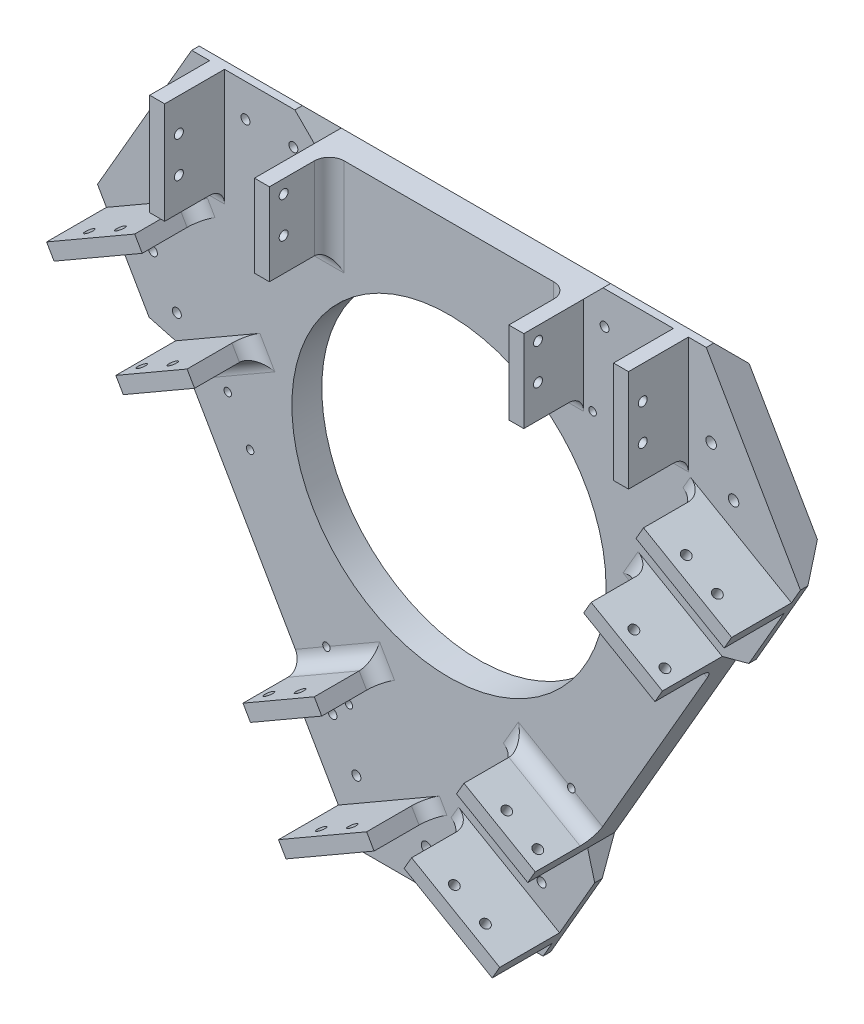
SolidWorks part; units mm, degrees
ref_plane "Plan de face" through (0, 0, 0) normal (0, 0, 1) x (1, 0, 0)
ref_plane "Plan de dessus" through (0, 0, 0) normal (0, 1, 0) x (1, 0, 0)
ref_plane "Plan de droite" through (0, 0, 0) normal (1, 0, 0) x (0, 0, -1)
sketch "Esquisse1" plane through (0, 0, 0) normal (0, 0, 1) x (1, 0, 0)
  line L0 (-85.9808, 85.9808) -> (85.9808, 85.9808)
  line L1 (85.9808, 85.9808) -> (117.4519, 31.4711)
  line L2 (117.4519, 31.4711) -> (31.4711, -117.4519)
  line L3 (31.4711, -117.4519) -> (-31.4711, -117.4519)
  line L4 (-31.4711, -117.4519) -> (-117.4519, 31.4711)
  line L5 (-117.4519, 31.4711) -> (-85.9808, 85.9808)
  line L6 (0, 85.9808) -> (0, -85.9808) construction
  circle A0 centre (0, 0) radius 52.5
  circle A1 centre (0, 0) radius 85.9808 construction
  point P6 (0, -117.4519)
  point P11 (0, 85.9808)
  point P12 (-74.4615, -42.9904)
  point P13 (74.4615, -42.9904)
  dimension "D1" = 105
  dimension "D2" = 117.4519
extrude "Boss.-Extru.1" add sketch "Esquisse1" along normal blind 10
sketch "Esquisse2" plane through (0, 0, 10) normal (0, 0, 1) x (1, 0, 0)
  line L0 (85.9808, 85.9808) -> (-85.9808, 85.9808) construction
  line L1 (80, 85.9808) -> (75, 85.9808)
  line L2 (80, 85.9808) -> (80, 51.9808)
  line L3 (80, 51.9808) -> (75, 51.9808)
  line L4 (75, 85.9808) -> (75, 51.9808)
  line L5 (80, 85.9808) -> (85.9808, 85.9808) construction
  line L6 (45, 85.9808) -> (40, 85.9808)
  line L7 (45, 85.9808) -> (45, 51.9808)
  line L8 (45, 51.9808) -> (40, 51.9808)
  line L9 (40, 85.9808) -> (40, 51.9808)
  line L10 (-40, 85.9808) -> (-45, 85.9808)
  line L11 (-40, 85.9808) -> (-40, 51.9808)
  line L12 (-40, 51.9808) -> (-45, 51.9808)
  line L13 (-45, 85.9808) -> (-45, 51.9808)
  line L14 (-75, 85.9808) -> (-80, 85.9808)
  line L15 (-75, 85.9808) -> (-75, 51.9808)
  line L16 (-75, 51.9808) -> (-80, 51.9808)
  line L17 (-80, 85.9808) -> (-80, 51.9808)
  line L18 (-85.9808, 85.9808) -> (-80, 85.9808) construction
  line L19 (34.4615, -112.2724) -> (5.0167, -95.2724)
  line L20 (34.4615, -112.2724) -> (36.9615, -107.9423)
  line L21 (36.9615, -107.9423) -> (7.5167, -90.9423)
  line L22 (5.0167, -95.2724) -> (7.5167, -90.9423)
  line L23 (51.9615, -81.9615) -> (22.5167, -64.9615)
  line L24 (51.9615, -81.9615) -> (54.4615, -77.6314)
  line L25 (54.4615, -77.6314) -> (25.0167, -60.6314)
  line L26 (22.5167, -64.9615) -> (25.0167, -60.6314)
  line L27 (94.4615, -8.3494) -> (65.0167, 8.6506)
  line L28 (94.4615, -8.3494) -> (96.9615, -4.0192)
  line L29 (96.9615, -4.0192) -> (67.5167, 12.9808)
  line L30 (65.0167, 8.6506) -> (67.5167, 12.9808)
  line L31 (111.9615, 21.9615) -> (82.5167, 38.9615)
  line L32 (111.9615, 21.9615) -> (114.4615, 26.2917)
  line L33 (114.4615, 26.2917) -> (85.0167, 43.2917)
  line L34 (82.5167, 38.9615) -> (85.0167, 43.2917)
  line L35 (-114.4615, 26.2917) -> (-85.0167, 43.2917)
  line L36 (-114.4615, 26.2917) -> (-111.9615, 21.9615)
  line L37 (-111.9615, 21.9615) -> (-82.5167, 38.9615)
  line L38 (-85.0167, 43.2917) -> (-82.5167, 38.9615)
  line L39 (-96.9615, -4.0192) -> (-67.5167, 12.9808)
  line L40 (-96.9615, -4.0192) -> (-94.4615, -8.3494)
  line L41 (-94.4615, -8.3494) -> (-65.0167, 8.6506)
  line L42 (-67.5167, 12.9808) -> (-65.0167, 8.6506)
  line L43 (-54.4615, -77.6314) -> (-25.0167, -60.6314)
  line L44 (-54.4615, -77.6314) -> (-51.9615, -81.9615)
  line L45 (-51.9615, -81.9615) -> (-22.5167, -64.9615)
  line L46 (-25.0167, -60.6314) -> (-22.5167, -64.9615)
  line L47 (-36.9615, -107.9423) -> (-7.5167, -90.9423)
  line L48 (-36.9615, -107.9423) -> (-34.4615, -112.2724)
  line L49 (-34.4615, -112.2724) -> (-5.0167, -95.2724)
  line L50 (-7.5167, -90.9423) -> (-5.0167, -95.2724)
  point P56 (0, 0)
  dimension "D1" = 5
  dimension "D2" = 30
  dimension "D3" = 30
  dimension "D4" = 34
  dimension "D5" = 80
  dimension "D6" = 3
extrude "Boss.-Extru.2" add sketch "Esquisse2" along normal blind 20
fillet "Congé1" radius 5 18 edges at (-40, 68.9808, 10) (-42.5, 51.9808, 10) (-77.5, 51.9808, 10) (-83.7667, 41.1266, 10) (-79.7391, 0.1506, 10) (-66.2667, 10.8157, 10) (-39.7391, -69.1314, 10) (-23.7667, -62.7965, 10) (-6.2667, -93.1073, 10) (6.2667, -93.1073, 10) (23.7667, -62.7965, 10) (39.7391, -69.1314, 10) (79.7391, 0.1506, 10) (66.2667, 10.8157, 10) (83.7667, 41.1266, 10) (77.5, 51.9808, 10) (42.5, 51.9808, 10) (40, 68.9808, 10)
sketch "Esquisse3" plane through (-80, 0, 0) normal (-1, 0, 0) x (0, 0, 1)
  line L0 (30, 51.9808) -> (15, 51.9808) construction
  line L1 (10, 85.9808) -> (10, 46.9808) construction
  circle A0 centre (25.25, 74.9808) radius 1.5
  circle A1 centre (25.25, 62.9808) radius 1.5
  dimension "D1" = 3
  dimension "D2" = 12
  dimension "D3" = 11
  dimension "D4" = 15.25
extrude "Enlèv. mat.-Extru.1" cut sketch "Esquisse3" against normal through all
sketch "Esquisse4" plane through (0, 0, 0) normal (0, 0, -1) x (-1, 0, 0)
  line L0 (45, 85.9808) -> (75, 85.9808) construction
  line L1 (45, 85.9808) -> (75, 85.9808) construction
  line L2 (68, 74.9808) -> (52, 74.9808) construction
  line L3 (60, 74.9808) -> (60, 85.9808) construction
  line L4 (-75, 85.9808) -> (-45, 85.9808) construction
  line L5 (-75, 85.9808) -> (-45, 85.9808) construction
  line L6 (-52, 74.9808) -> (-68, 74.9808) construction
  line L7 (-60, 74.9808) -> (-60, 85.9808) construction
  circle A0 centre (68, 74.9808) radius 1.5
  circle A1 centre (52, 74.9808) radius 1.5
  circle A2 centre (-52, 74.9808) radius 1.5
  circle A3 centre (-68, 74.9808) radius 1.5
  dimension "D1" = 3
  dimension "D2" = 16
  dimension "D3" = 11
extrude "Enlèv. mat.-Extru.2" cut sketch "Esquisse4" against normal up to next
sketch "Esquisse5" plane through (0, 0, 0) normal (0, 0, -1) x (-1, 0, 0)
  circle A0 centre (68, 74.9808) radius 3
  circle A1 centre (52, 74.9808) radius 3
  circle A2 centre (-52, 74.9808) radius 3
  circle A3 centre (-68, 74.9808) radius 3
  dimension "D1" = 6
extrude "Enlèv. mat.-Extru.3" cut sketch "Esquisse5" against normal blind 4.25
sketch "Esquisse6" plane through (0, 0, 0) normal (0, 0, -1) x (-1, 0, 0)
  line L0 (-85.9808, 85.9808) -> (85.9808, 85.9808) construction
  line L1 (45, 85.9808) -> (-45, 85.9808)
  line L2 (45, 85.9808) -> (45, 79.4808)
  line L3 (45, 79.4808) -> (-45, 79.4808)
  line L4 (-45, 85.9808) -> (-45, 79.4808)
  dimension "D1" = 6.5
extrude "Enlèv. mat.-Extru.4" cut sketch "Esquisse6" against normal up to next
pattern_circular "Répétition circulaire3" count 3 over 360 about axis through (0, 0, 0) along (0, 0, 1) of "Enlèv. mat.-Extru.1", "Enlèv. mat.-Extru.3", "Enlèv. mat.-Extru.2", "Enlèv. mat.-Extru.4"
chamfer "Chanfrein1" distance 6.5 angle 45 18 edges at (-49.1469, -80.3365, 10) (45, 82.7308, 10) (-45, 85.9808, 5) (45, 85.9808, 5) (-45, 82.7308, 0) (45, 82.7308, 0) (-45, 82.7308, 10) (-51.9615, -81.9615, 5) (-94.1469, -2.3942, 10) (-96.9615, -4.0192, 5) (-49.1469, -80.3365, 0) (-94.1469, -2.3942, 0) (96.9615, -4.0192, 5) (49.1469, -80.3365, 10) (51.9615, -81.9615, 5) (94.1469, -2.3942, 0) (49.1469, -80.3365, 0) (94.1469, -2.3942, 10)
chamfer "Chanfrein2" distance 7.5 angle 45 3 edges at (-68.7404, 85.9808, 0) (108.8317, 16.5405, 0) (-108.8317, 16.5405, 0)
sketch "Esquisse7" plane through (0, 0, 0) normal (0, 0, -1) x (-1, 0, 0)
  line L0 (95.1157, 46.2548) -> (87.6157, 59.2452) construction
  line L1 (91.3657, 52.75) -> (101.7163, 58.726) construction
  line L2 (90.3109, 78.4808) -> (113.1218, 38.9711) construction
  circle A0 centre (95.1157, 46.2548) radius 1.75
  circle A1 centre (87.6157, 59.2452) radius 1.75
  dimension "D1" = 3.5
  dimension "D2" = 11.9519
  dimension "D3" = 15
extrude "Enlèv. mat.-Extru.5" cut sketch "Esquisse7" against normal up to next
sketch "Esquisse8" plane through (0, 0, 0) normal (0, 0, -1) x (-1, 0, 0)
  circle A0 centre (95.1157, 46.2548) radius 3.5
  circle A1 centre (87.6157, 59.2452) radius 3.5
  dimension "D1" = 7
extrude "Enlèv. mat.-Extru.6" cut sketch "Esquisse8" against normal blind 4
pattern_circular "Répétition circulaire4" count 3 over 360 about axis through (0, 0, 0) along (0, 0, 1) of "Enlèv. mat.-Extru.6", "Enlèv. mat.-Extru.5"
sketch "Esquisse9" plane through (0, 0, 0) normal (0, 0, -1) x (-1, 0, 0)
  line L0 (0, 0) -> (67.9663, -39.2404) construction
  line L1 (22.8109, -117.4519) -> (113.1218, 38.9711) construction
  line L2 (0, 0) -> (-67.9663, -39.2404) construction
  line L3 (-113.1218, 38.9711) -> (-22.8109, -117.4519) construction
  line L4 (33.4401, -77.0417) -> (40.9401, -64.0513) construction
  line L5 (40.9401, -64.0513) -> (66.4401, -19.884) construction
  line L6 (66.4401, -19.884) -> (73.9401, -6.8936) construction
  line L7 (-73.9401, -6.8936) -> (-66.4401, -19.884) construction
  line L8 (-66.4401, -19.884) -> (-40.9401, -64.0513) construction
  line L9 (-40.9401, -64.0513) -> (-33.4401, -77.0417) construction
  line L10 (-48, 48.4808) -> (-58, 48.4808) construction
  line L11 (-58, 48.4808) -> (-58, 38.4808) construction
  line L12 (48, 48.4808) -> (58, 48.4808) construction
  line L13 (58, 48.4808) -> (58, 38.4808) construction
  line L14 (-48, 48.4808) -> (48, 48.4808) construction
  line L15 (90.3109, 78.4808) -> (-90.3109, 78.4808) construction
  circle A0 centre (33.4401, -77.0417) radius 1.25
  circle A1 centre (40.9401, -64.0513) radius 1.25
  circle A2 centre (66.4401, -19.884) radius 1.25
  circle A3 centre (73.9401, -6.8936) radius 1.25
  circle A4 centre (-73.9401, -6.8936) radius 1.25
  circle A5 centre (-66.4401, -19.884) radius 1.25
  circle A6 centre (-40.9401, -64.0513) radius 1.25
  circle A7 centre (-33.4401, -77.0417) radius 1.25
  circle A8 centre (-58, 38.4808) radius 1.25
  circle A9 centre (-48, 48.4808) radius 1.25
  circle A10 centre (48, 48.4808) radius 1.25
  circle A11 centre (58, 38.4808) radius 1.25
  point P32 (0, 48.4808)
  point P37 (0, 78.4808)
  dimension "D5" = 2.5
  dimension "D1" = 15
  dimension "D2" = 50
  dimension "D3" = 15
  dimension "D4" = 31
  dimension "D6" = 11
  dimension "D7" = 11
  dimension "D8" = 50
  dimension "D9" = 15
  dimension "D10" = 15
  dimension "D11" = 31
  dimension "D12" = 10
  dimension "D13" = 10
  dimension "D14" = 40
  dimension "D15" = 116
extrude "Enlèv. mat.-Extru.7" cut sketch "Esquisse9" against normal up to next
